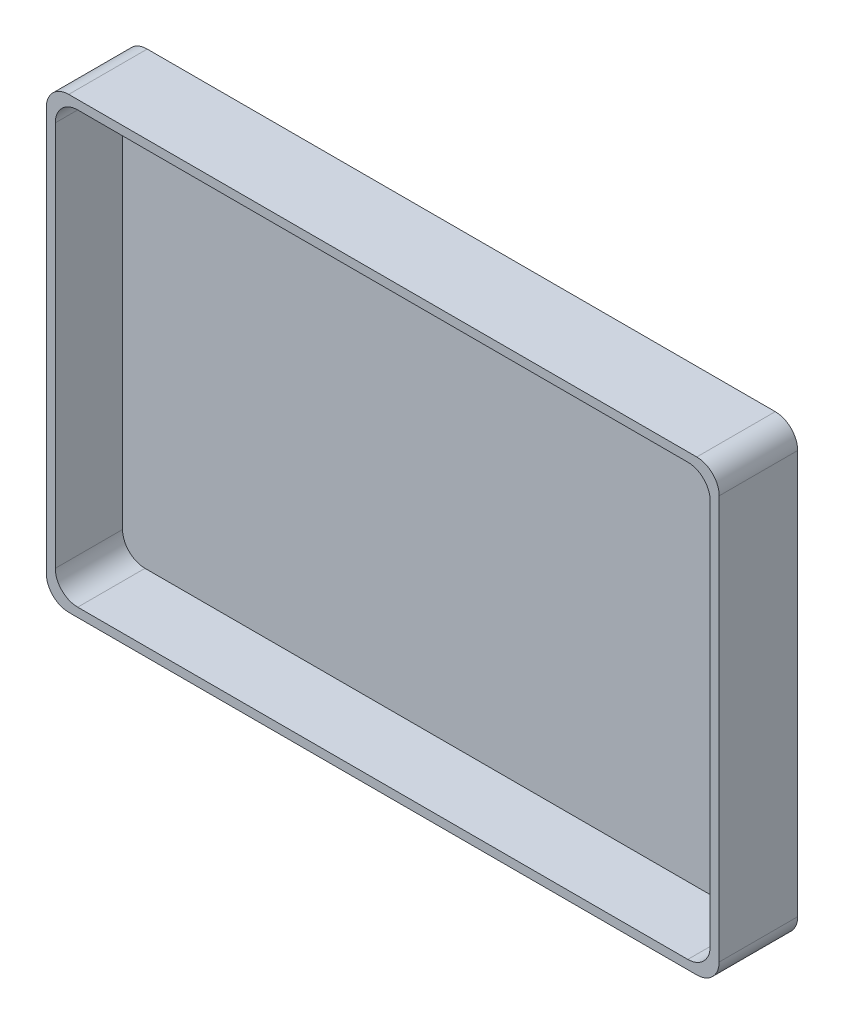
SolidWorks part; units mm, degrees
ref_plane "Plan de face" through (0, 0, 0) normal (0, 0, 1) x (1, 0, 0)
ref_plane "Plan de dessus" through (0, 0, 0) normal (0, 1, 0) x (1, 0, 0)
ref_plane "Plan de droite" through (0, 0, 0) normal (1, 0, 0) x (0, 0, -1)
sketch "Esquisse1" plane through (0, 0, 0) normal (0, 0, 1) x (1, 0, 0)
  line L1 (0, 0) -> (600, 0)
  line L2 (0, 0) -> (0, 400)
  line L3 (0, 400) -> (600, 400)
  line L4 (600, 0) -> (600, 400)
  dimension "D1" = 600
  dimension "D2" = 400
extrude "Boss.-Extru.1" add sketch "Esquisse1" along normal blind 10
sketch "Esquisse2" plane through (0, 0, 10) normal (0, 0, 1) x (1, 0, 0)
  line L0 (8, 392) -> (8, 8)
  line L1 (8, 8) -> (592, 8)
  line L2 (592, 8) -> (592, 392)
  line L3 (592, 392) -> (8, 392)
  line L4 (0, 400) -> (0, 0)
  line L5 (0, 0) -> (600, 0)
  line L6 (600, 0) -> (600, 400)
  line L7 (600, 400) -> (0, 400)
  line L8 (0, 400) -> (0, 0)
  line L9 (0, 0) -> (600, 0)
  line L10 (600, 0) -> (600, 400)
  line L11 (600, 400) -> (0, 400)
  dimension "D1" = 0
  dimension "D2" = 8
extrude "Boss.-Extru.2" add sketch "Esquisse2" along normal blind 60
fillet "Congé1" radius 20 8 edges at (8, 8, 40) (0, 0, 35) (8, 392, 40) (0, 400, 35) (600, 400, 35) (592, 392, 40) (592, 8, 40) (600, 0, 35)
